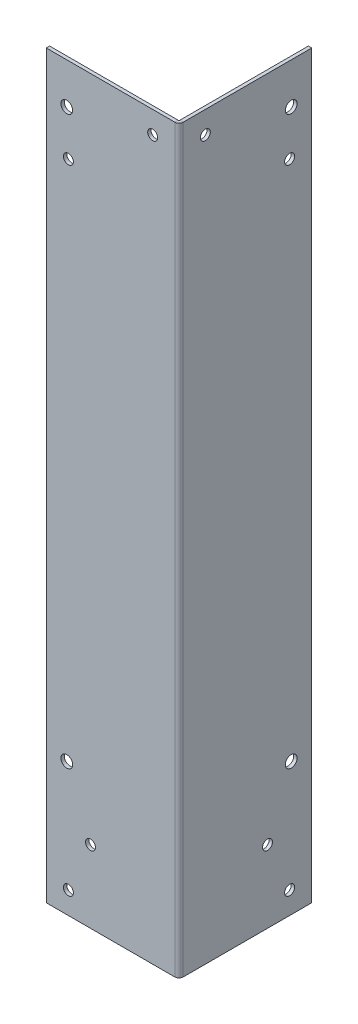
SolidWorks part; units mm, degrees
note: The reader was unsure of these and kept them because the rebuilt part matched: flange length of "Edge-Flange1".
material "AISI 304"
ref_plane "Front Plane" through (0, 0, 0) normal (0, 0, 1) x (1, 0, 0)
ref_plane "Top Plane" through (0, 0, 0) normal (0, 1, 0) x (1, 0, 0)
ref_plane "Right Plane" through (0, 0, 0) normal (1, 0, 0) x (0, 0, -1)
sketch "Sketch1" plane through (0, 0, 0) normal (1, 0, 0) x (0, 0, -1)
  line L1 (0, 0) -> (-60, 0)
  line L2 (0, 0) -> (0, 334.6139)
  line L3 (0, 334.6139) -> (-60, 334.6139)
  line L4 (-60, 0) -> (-60, 334.6139)
  dimension "D1" = 60
  dimension "D2" = 334.6139
base flange "Base-Flange1" sketch "Sketch1" thickness 1.5189 reverse thickness direction no parameters "D1"=0.381
edge flange "Edge-Flange1" sketch "Sketch8" flange angle 90 flange length 60 flange position material inside bend radius 0.381 thickness 1.5189 relief rectangular parameters "D6"=10
sketch "Sketch8" plane through (-1.5189, 0, 60) normal (0, 0, 1) x (0, 1, 0)
  line L0 (334.6139, 0) -> (0, 0) construction
  line L1 (334.6139, 0) -> (0, 0)
  line L2 (0, 0) -> (0, 58.4811)
  line L3 (0, 58.4811) -> (334.6139, 58.4811)
  line L4 (334.6139, 58.4811) -> (334.6139, 0)
bend "EdgeBend1" bend radius 0.381 bend angle 90 parameters "D5"=1
hole_wizard "M5 Clearance Hole1" positions "Sketch10" profile "Sketch9" hole size "M5" standard "ANSI Metric" end condition through all
sketch "Sketch10" plane through (0, 0, 60) normal (0, 0, 1) x (1, 0, 0)
  line L0 (0, 334.6139) -> (0, 0) construction
  line L1 (-60, 0) -> (-1.8999, 0) construction
  line L2 (-1.8999, 334.6139) -> (-60, 334.6139) construction
  point P0 (-50.726, 60)
  point P7 (-50.726, 316.1328)
  dimension "D1" = 50.726
  dimension "D2" = 60
  dimension "D3" = 18.4811
sketch "Sketch9" plane through (-50.726, 60, 60) normal (1, 0, 0) x (0, -1, 0)
  line L0 (0, 0) -> (0, 60)
  line L1 (0, 60) -> (2.65, 60)
  line L2 (2.65, 60) -> (2.65, 0)
  line L5 (2.65, 0) -> (0, 0)
  line L11 (0, -6.35) -> (0, 107.95) construction
  dimension "Thru Hole Dia." = 5.3
  dimension "Thru Hole Depth" = 60
hole_wizard "M5 Clearance Hole2" positions "Sketch12" profile "Sketch11" hole size "M5" standard "ANSI Metric" end condition through all
sketch "Sketch12" plane through (0, 0, 0) normal (1, 0, 0) x (0, 0, -1)
  line L0 (-60, 334.6139) -> (-60, 0) construction
  line L1 (-58.1001, 0) -> (0, 0) construction
  line L2 (0, 334.6139) -> (-58.1001, 334.6139) construction
  point P0 (-9.274, 60)
  point P7 (-9.274, 316.1328)
  dimension "D1" = 50.726
  dimension "D2" = 60
  dimension "D3" = 18.4811
sketch "Sketch11" plane through (0, 60, 9.274) normal (0, 1, 0) x (0, 0, -1)
  line L0 (0, 0) -> (0, 60)
  line L1 (0, 60) -> (2.65, 60)
  line L2 (2.65, 60) -> (2.65, 0)
  line L5 (2.65, 0) -> (0, 0)
  line L11 (0, -6.35) -> (0, 107.95) construction
  dimension "Thru Hole Dia." = 5.3
  dimension "Thru Hole Depth" = 60
hole_wizard "M4 Clearance Hole1" positions "Sketch14" profile "Sketch13" hole size "M4" standard "ANSI Metric" end condition through all
sketch "Sketch14" plane through (0, 0, 60) normal (0, 0, 1) x (1, 0, 0)
  line L0 (-50, 10) -> (-50, 32.714) construction
  line L1 (-50, 32.714) -> (-40, 32.714) construction
  line L4 (-50, 296.1328) -> (-50, 324.6139) construction
  line L5 (-50, 324.6139) -> (-11.8999, 324.6139) construction
  line L7 (-1.8999, 334.6139) -> (-60, 334.6139) construction
  line L8 (-1.8999, 334.6139) -> (-1.8999, 0) construction
  line L9 (-60, 334.6139) -> (-60, 0) construction
  line L11 (-26.5189, 286.1328) -> (-366.3188, 286.1328) construction
  line L12 (-60, 0) -> (-1.8999, 0) construction
  line L13 (-26.5189, 42.714) -> (-366.3188, 42.714) construction
  point P0 (-50, 296.1328)
  point P2 (-11.8999, 324.6139)
  point P4 (-50, 10)
  point P6 (-40, 32.714)
  dimension "D1" = 10
  dimension "D2" = 10
  dimension "D3" = 10
  dimension "D4" = 10
  dimension "D5" = 10
  dimension "D6" = 10
  dimension "D7" = 10
sketch "Sketch13" plane through (-50, 296.1328, 60) normal (1, 0, 0) x (0, -1, 0)
  line L0 (0, 0) -> (0, 60)
  line L1 (0, 60) -> (2.25, 60)
  line L2 (2.25, 60) -> (2.25, 0)
  line L5 (2.25, 0) -> (0, 0)
  line L11 (0, -6.35) -> (0, 107.95) construction
  dimension "Thru Hole Dia." = 4.5
  dimension "Thru Hole Depth" = 60
hole_wizard "M4 Clearance Hole2" positions "Sketch16" profile "Sketch15" hole size "M4" standard "ANSI Metric" end condition through all
sketch "Sketch16" plane through (0, 0, 0) normal (1, 0, 0) x (0, 0, -1)
  line L0 (-58.1001, 334.6139) -> (-58.1001, 0) construction
  line L1 (-33.4811, 42.714) -> (310.3188, 42.714) construction
  line L2 (0, 0) -> (0, 334.6139) construction
  line L3 (-58.1001, 0) -> (0, 0) construction
  line L4 (0, 334.6139) -> (-58.1001, 334.6139) construction
  line L5 (310.3188, 286.1328) -> (-33.4811, 286.1328) construction
  point P0 (-10, 296.1328)
  point P2 (-48.1001, 324.6139)
  point P4 (-10, 10)
  point P6 (-20, 32.714)
  dimension "D1" = 10
  dimension "D2" = 10
  dimension "D3" = 10
  dimension "D4" = 10
  dimension "D5" = 10
  dimension "D6" = 10
  dimension "D7" = 10
  dimension "D8" = 10
sketch "Sketch15" plane through (0, 296.1328, 10) normal (0, 1, 0) x (0, 0, -1)
  line L0 (0, 0) -> (0, 60)
  line L1 (0, 60) -> (2.25, 60)
  line L2 (2.25, 60) -> (2.25, 0)
  line L5 (2.25, 0) -> (0, 0)
  line L11 (0, -6.35) -> (0, 107.95) construction
  dimension "Thru Hole Dia." = 4.5
  dimension "Thru Hole Depth" = 60
sketch "Bend-Lines1" [suppressed] plane through (0, 0, 0) normal (0, 1, 0) x (1, 0, 0)
sketch "Bounding-Box1" [suppressed] plane through (0, 0, 0) normal (0, 1, 0) x (1, 0, 0)
sheet metal parameters "Sheet-Metal1" thickness 1.5189 parameters "D1"=1.905
flat pattern "Flat-Pattern1" [suppressed]
sketch "Bend-Lines2" plane through (0, 0, 0) normal (0, 1, 0) x (1, 0, 0)
sketch3d "Bounding-Box2" [suppressed]
  line L0 (0, 500, 0) -> (0, 0, 0) construction
  line L1 (60, 500, 0) -> (60, 0, 0) construction
  line L2 (0, 500, 0) -> (60, 500, 0) construction
  line L3 (0, 0, 0) -> (60, 0, 0) construction
sheet metal parameters "Sheet-Metal2" thickness 1.5189 parameters "D1"=1.905
flat pattern "Flat-Pattern1"
sketch "Bend-Lines2" plane through (0, 0, 0) normal (1, 0, 0) x (0, 0, -1)
  line L0 (-62.0927, 500) -> (-62.0927, 0) construction
  line L1 (-62.0927, 500) -> (-62.0927, 0) construction
sketch3d "Bounding-Box2" [suppressed]
  line L0 (0, 500, 0) -> (0, 0, 0) construction
  line L1 (-120.7614, 500, 0) -> (-120.7614, 0, 0) construction
  line L2 (0, 500, 0) -> (-120.7614, 500, 0) construction
  line L3 (0, 0, 0) -> (-120.7614, 0, 0) construction
bend of the flat pattern "Flatten-<EdgeBend1>1"
sheet metal parameters "Sheet-Metal3" thickness 1.5189 parameters "D1"=1.905
flat pattern "Flat-Pattern1"
sketch "Bend-Lines2" plane through (0, 0, 0) normal (1, 0, 0) x (0, 0, -1)
  line L0 (-62.0927, 334.6139) -> (-62.0927, 0) construction
  line L1 (-62.0927, 334.6139) -> (-62.0927, 0) construction
sketch3d "Bounding-Box2" [suppressed]
  line L0 (0, 334.6139, 0) -> (0, 0, 0) construction
  line L1 (-120.7614, 334.6139, 0) -> (-120.7614, 0, 0) construction
  line L2 (0, 334.6139, 0) -> (-120.7614, 334.6139, 0) construction
  line L3 (0, 0, 0) -> (-120.7614, 0, 0) construction
bend of the flat pattern "Flatten-<EdgeBend1>1"
sheet metal parameters "Sheet-Metal4" thickness 1.5189 parameters "D1"=1.905
flat pattern "Flat-Pattern1"
sketch "Bend-Lines2" plane through (0, 0, 0) normal (1, 0, 0) x (0, 0, -1)
  line L0 (-62.0927, 334.6139) -> (-62.0927, 0) construction
  line L1 (-62.0927, 334.6139) -> (-62.0927, 0) construction
sketch3d "Bounding-Box2" [suppressed]
  line L0 (0, 334.6139, 0) -> (0, 0, 0) construction
  line L1 (-120.7614, 334.6139, 0) -> (-120.7614, 0, 0) construction
  line L2 (0, 334.6139, 0) -> (-120.7614, 334.6139, 0) construction
  line L3 (0, 0, 0) -> (-120.7614, 0, 0) construction
bend of the flat pattern "Flatten-<EdgeBend1>1"
sheet metal parameters "Sheet-Metal5" thickness 1.5189 parameters "D1"=1.905
flat pattern "Flat-Pattern1"
sketch "Bend-Lines2" plane through (0, 0, 0) normal (1, 0, 0) x (0, 0, -1)
  line L0 (-62.0927, 334.6139) -> (-62.0927, 0) construction
  line L1 (-62.0927, 334.6139) -> (-62.0927, 0) construction
sketch3d "Bounding-Box2" [suppressed]
  line L0 (0, 334.6139, 0) -> (0, 0, 0) construction
  line L1 (-120.7614, 334.6139, 0) -> (-120.7614, 0, 0) construction
  line L2 (0, 334.6139, 0) -> (-120.7614, 334.6139, 0) construction
  line L3 (0, 0, 0) -> (-120.7614, 0, 0) construction
bend of the flat pattern "Flatten-<EdgeBend1>1"
sheet metal parameters "Sheet-Metal6" thickness 1.5189 parameters "D1"=1.905
flat pattern "Flat-Pattern1"
sketch "Bend-Lines2" plane through (0, 0, 0) normal (1, 0, 0) x (0, 0, -1)
  line L0 (-58.9958, 334.6139) -> (-58.9958, 0) construction
  line L1 (-58.9958, 334.6139) -> (-58.9958, 0) construction
sketch3d "Bounding-Box2" [suppressed]
  line L0 (0, 334.6139, 0) -> (0, 0, 0) construction
  line L1 (-117.9916, 334.6139, 0) -> (-117.9916, 0, 0) construction
  line L2 (0, 334.6139, 0) -> (-117.9916, 334.6139, 0) construction
  line L3 (0, 0, 0) -> (-117.9916, 0, 0) construction
bend of the flat pattern "Flatten-<EdgeBend1>1"
